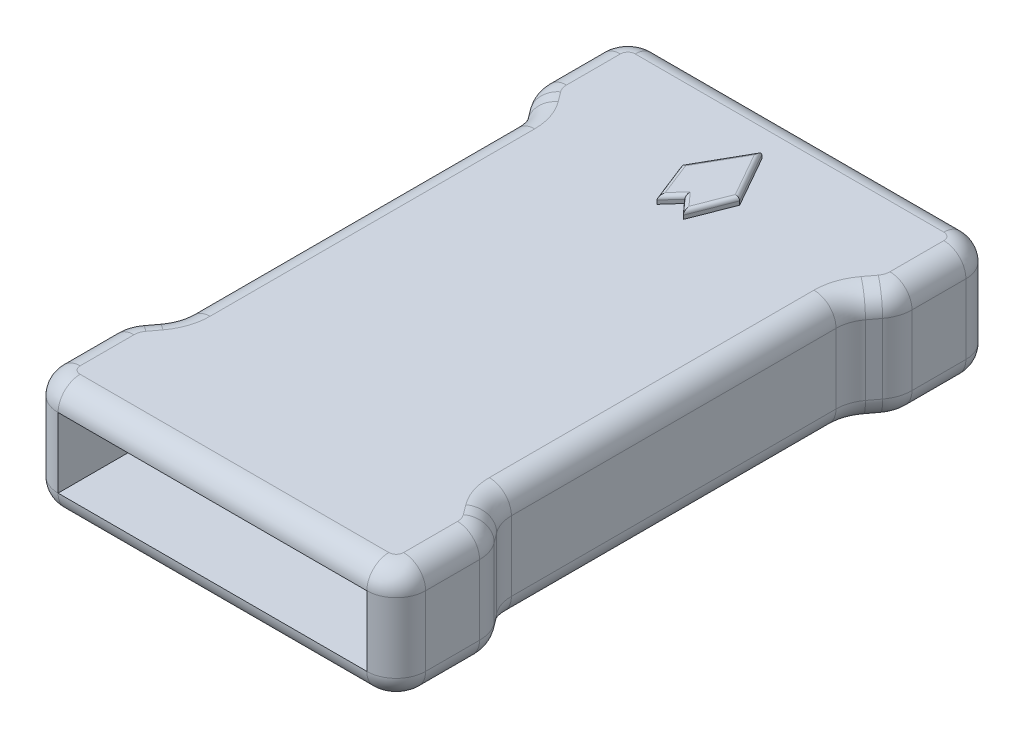
SolidWorks part; units mm, degrees
note: The reader was unsure of these and kept them because the rebuilt part matched: shared geometry of "Sketch2<6>".
material "PF"
ref_plane "Front Plane" through (0, 0, 0) normal (0, 0, 1) x (1, 0, 0)
ref_plane "Top Plane" through (0, 0, 0) normal (0, 1, 0) x (1, 0, 0)
ref_plane "Right Plane" through (0, 0, 0) normal (1, 0, 0) x (0, 0, -1)
other "Center of Mass" [suppressed]
sketch "Sketch1" plane through (0, 0, 0) normal (0, 1, 0) x (1, 0, 0)
  line L1 (-25, -40.75) -> (25, -40.75)
  line L2 (-25, -40.75) -> (-25, 40.75)
  line L3 (-25, 40.75) -> (25, 40.75)
  line L4 (25, -40.75) -> (25, 40.75)
  line L5 (-25, -40.75) -> (25, 40.75) construction
  line L6 (-25, 40.75) -> (25, -40.75) construction
  point P0 (0, 0)
  dimension "D1" = 50
  dimension "D2" = 81.5
extrude "Boss-Extrude1" add sketch "Sketch1" along normal blind 15.5
sketch "Sketch2" plane through (0, 15.5, 0) normal (0, 1, 0) x (-1, 0, 0)
  line L0 (0, -1000) -> (0, 49000) construction
  line L1 (-25, 27.75) -> (-22, 23.75)
  line L2 (-25, 40.75) -> (-25, -40.75) construction
  line L3 (-22, 23.75) -> (-22, -23.75)
  line L4 (25, 40.75) -> (-25, 40.75) construction
  line L5 (-1000, 0) -> (49000, 0) construction
  line L6 (-25, -27.75) -> (-22, -23.75)
  line L7 (25, -27.75) -> (22, -23.75)
  line L8 (22, 23.75) -> (22, -23.75)
  line L9 (25, 27.75) -> (22, 23.75)
  point P14 (-22, 0)
  line M3 (25, -40.75) -> (25, 40.75)
  dimension "D1" = 3
  dimension "D2" = 13
  dimension "D3" = 17
extrude "Cut-Extrude4" cut sketch "Sketch2" against normal through all contours L1 L3 L6
extrude "Cut-Extrude5" cut sketch "Sketch2<6>" against normal through all contours L9 L8 L7 M3
sketch "Sketch2<6>" plane through (0, 15.5, 0) normal (0, 1, 0) x (-1, 0, 0) same geometry as "Sketch2"
fillet "Fillet1" radius 5 8 edges at (-25, 7.75, -27.75) (-22, 7.75, -23.75) (-22, 7.75, 23.75) (-25, 7.75, 27.75) (25, 7.75, -27.75) (22, 7.75, -23.75) (22, 7.75, 23.75) (25, 7.75, 27.75)
fillet "Fillet3" radius 4 4 edges at (25, 7.75, 40.75) (-25, 7.75, 40.75) (-25, 7.75, -40.75) (25, 7.75, -40.75)
fillet "Fillet4" radius 3 48 edges at (24.7434, 0, 27.8355) (23.5, 0, 25.75) (22.2566, 0, 23.6645) (22, 0, 0) (22.2566, 0, -23.6645) (23.5, 0, -25.75) (24.7434, 0, -27.8355) (25, 0, -33.0833) (23.8284, 0, -39.5784) (0, 0, -40.75) (-23.8284, 0, -39.5784) (-25, 0, -33.0833) (-24.7434, 0, -27.8355) (-23.5, 0, -25.75) (-22.2566, 0, -23.6645) (-22, 0, 0) (-22.2566, 0, 23.6645) (-23.5, 0, 25.75) (-24.7434, 0, 27.8355) (-25, 0, 33.0833) (-23.8284, 0, 39.5784) (0, 0, 40.75) (23.8284, 0, 39.5784) (25, 0, 33.0833) (-23.8284, 15.5, 39.5784) (-25, 15.5, 33.0833) (-24.7434, 15.5, 27.8355) (-23.5, 15.5, 25.75) (-22.2566, 15.5, 23.6645) (-22, 15.5, 0) (-22.2566, 15.5, -23.6645) (-23.5, 15.5, -25.75) (-24.7434, 15.5, -27.8355) (-25, 15.5, -33.0833) (-23.8284, 15.5, -39.5784) (0, 15.5, -40.75) (23.8284, 15.5, -39.5784) (25, 15.5, -33.0833) (24.7434, 15.5, -27.8355) (23.5, 15.5, -25.75) (22.2566, 15.5, -23.6645) (22, 15.5, 0) (22.2566, 15.5, 23.6645) (23.5, 15.5, 25.75) (24.7434, 15.5, 27.8355) (25, 15.5, 33.0833) (23.8284, 15.5, 39.5784) (0, 15.5, 40.75)
sketch "Sketch5" plane through (0, 15.5, 0) normal (0, 1, 0) x (-1, 0, 0)
  line L0 (0, -1000) -> (0, 49000)
  line L1 (0, -23.5064) -> (1.7812, -21.5179)
  line L2 (1.7812, -21.5179) -> (3.9378, -27.0338)
  line L3 (3.9378, -27.0338) -> (0, -33.9802)
  line L4 (0, -23.5064) -> (-1.7812, -21.5179)
  line L5 (-1.7812, -21.5179) -> (-3.9378, -27.0338)
  line L6 (-3.9378, -27.0338) -> (0, -33.9802)
extrude "Boss-Extrude2" add sketch "Sketch5" along normal blind 1 separate body
fillet "Fillet5" radius 0.5 6 edges at (-0.8906, 16.5, -22.5121) (-2.8595, 16.5, -24.2759) (-1.9689, 16.5, -30.507) (1.9689, 16.5, -30.507) (2.8595, 16.5, -24.2759) (0.8906, 16.5, -22.5121)
sketch "Sketch6" plane through (0, 0, 40.75) normal (0, 0, 1) x (1, 0, 0)
  line L1 (-21, 3) -> (21, 3)
  line L2 (-21, 3) -> (-21, 12.5)
  line L3 (-21, 12.5) -> (21, 12.5)
  line L4 (21, 3) -> (21, 12.5)
  line L5 (-21, 3) -> (21, 12.5) construction
  line L6 (-21, 12.5) -> (21, 3) construction
  point P0 (0, 7.75)
extrude "Cut-Extrude6" cut sketch "Sketch6" against normal blind 10
